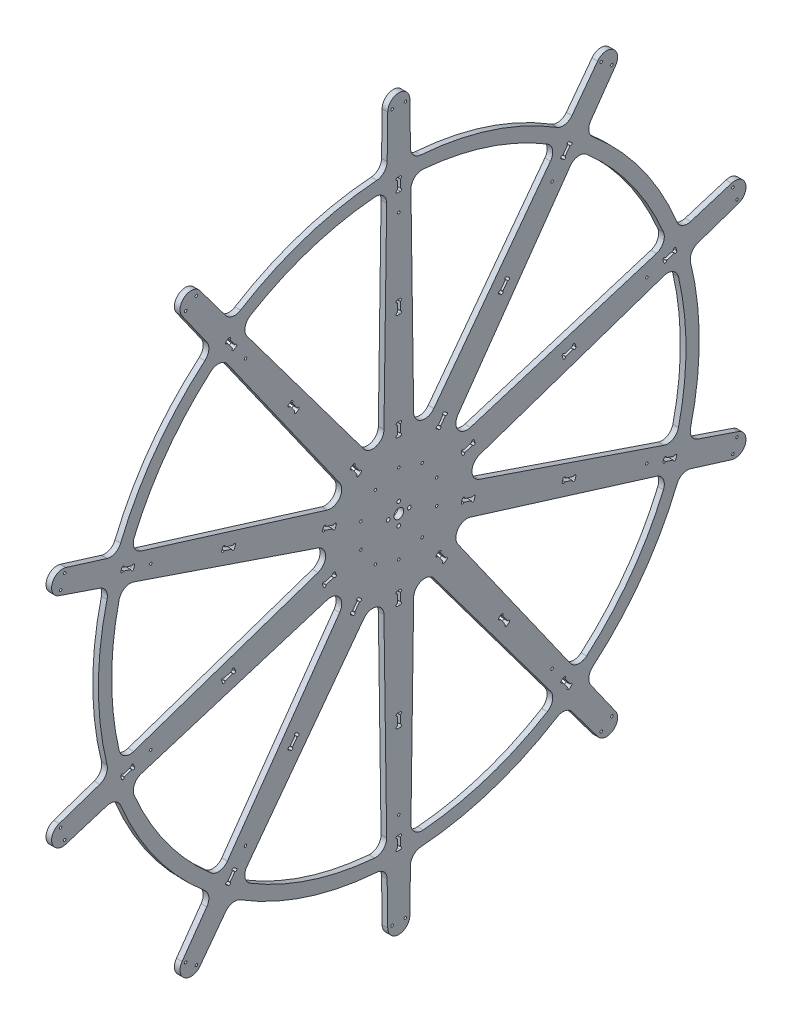
SolidWorks part; units mm, degrees
material "MDF"
ref_plane "Front Plane" through (0, 0, 0) normal (0, 0, 1) x (1, 0, 0)
ref_plane "Top Plane" through (0, 0, 0) normal (0, 1, 0) x (1, 0, 0)
ref_plane "Right Plane" through (0, 0, 0) normal (1, 0, 0) x (0, 0, -1)
sketch "Sketch1" plane through (0, 0, 0) normal (1, 0, 0) x (0, 0, -1)
  line L0 (0, 0) -> (0, -400) construction
  line L1 (-12.5, -400) -> (12.5, -400)
  line L2 (12.5, -400) -> (17.5, -41.4578)
  line L3 (-12.5, -400) -> (-17.5, -41.4578)
  line L4 (0, 0) -> (0, 12) construction
  line L5 (-1.6875, -210.2) -> (1.6875, -210.2)
  line L6 (-1.6875, -90.2) -> (1.6875, -90.2)
  line L7 (-1.6875, -90.2) -> (-1.6875, -75)
  line L8 (-1.6875, -75) -> (1.6875, -75)
  line L9 (1.6875, -90.2) -> (1.6875, -75)
  line L10 (-1.6875, -90.2) -> (1.6875, -75) construction
  line L11 (-1.6875, -75) -> (1.6875, -90.2) construction
  line L12 (-1.6875, -210.2) -> (-1.6875, -195)
  line L13 (-1.6875, -195) -> (1.6875, -195)
  line L14 (1.6875, -210.2) -> (1.6875, -195)
  line L15 (-1.6875, -210.2) -> (1.6875, -195) construction
  line L16 (-1.6875, -195) -> (1.6875, -210.2) construction
  line L17 (-1.6875, -330.2) -> (1.6875, -330.2)
  line L18 (-1.6875, -330.2) -> (-1.6875, -315)
  line L19 (-1.6875, -315) -> (1.6875, -315)
  line L20 (1.6875, -330.2) -> (1.6875, -315)
  line L21 (-1.6875, -330.2) -> (1.6875, -315) construction
  line L22 (-1.6875, -315) -> (1.6875, -330.2) construction
  line L23 (0, -82.6) -> (0, -202.6) construction
  circle A0 centre (0, 0) radius 45
  circle A1 centre (0, 0) radius 12 construction
  circle A2 centre (0, -400) radius 12.5
  circle A15 centre (1.6875, -76.397) radius 1.397
  circle A16 centre (-1.6875, -76.397) radius 1.397
  circle A17 centre (-1.6875, -88.803) radius 1.397
  circle A18 centre (1.6875, -88.803) radius 1.397
  circle A19 centre (1.6875, -196.397) radius 1.397
  circle A20 centre (-1.6875, -196.397) radius 1.397
  circle A21 centre (-1.6875, -208.803) radius 1.397
  circle A22 centre (1.6875, -208.803) radius 1.397
  circle A23 centre (1.6875, -316.397) radius 1.397
  circle A24 centre (-1.6875, -316.397) radius 1.397
  circle A25 centre (-1.6875, -328.803) radius 1.397
  circle A26 centre (1.6875, -328.803) radius 1.397
  point P8 (0, -400)
  point P12 (0, -82.6)
  point P18 (0, -322.6)
  point P19 (0, -202.6)
  point P28 (-7.5, -400)
  point P30 (7.5, -400)
  dimension "D2" = 24
  dimension "D5" = 90
  dimension "D6" = 12.5
  dimension "D13" = 2.794
  dimension "D1" = 400
  dimension "D3" = 25
  dimension "D4" = 35
  dimension "D7" = 15.2
  dimension "D8" = 3.375
  dimension "D9" = 75
  dimension "D11" = 120
  dimension "D12" = 5
  dimension "D10" = 3
extrude "Boss-Extrude1" add sketch "Sketch1" along normal mid plane 6.35 contours A0 region at (0, 0, 0)
extrude "Boss-Extrude2" add sketch "Sketch1<4>" against normal up to surface (3.175 mm away) from surface contours A0 L3 L1 L2 | L5 L14 L13 L12 | L17 L20 L19 L18 | L6 L9 L8 L7 | A2 | A0 region at (0, -220.6787, 11.3979) region at (0, -202.6, 0) region at (0, -82.6, 0) region at (0, -322.6, 0) up to face at (-3.175, 0, -45) starting at face at (3.175, 0, -45)
sketch "Sketch1<4>" plane through (0, 0, 0) normal (1, 0, 0) x (0, 0, -1) same geometry as "Sketch1"
sketch "Sketch2" plane through (0, 0, 0) normal (1, 0, 0) x (0, 0, -1)
  circle A0 centre (0, 0) radius 340
  circle A1 centre (0, 0) radius 325
  point P6 (0, -340)
  dimension "D1" = 60
  dimension "D2" = 15
extrude "Boss-Extrude3" add sketch "Sketch2" against normal up to surface (3.175 mm away) from surface contours A0 A1 region at (0, 0, 330.3833) up to face at (-3.175, -202.2395, 0) starting at face at (3.175, -202.2395, 0)
sketch "Sketch3" plane through (-3.175, 0, 0) normal (1, 0, 0) x (0, 0, -1)
  point P0 (0, 12)
extrude "Cut-Extrude1" cut sketch "Sketch1<5>" against normal through all both and the other way through all contours L18 A25 | L20 A26 | L9 L8 L7 L6 | L14 L13 L12 L5 | L20 L19 L18 L17 region at (0, -328.803, 2.2804) region at (0, -328.803, -2.2804)
sketch "Sketch1<5>" plane through (0, 0, 0) normal (1, 0, 0) x (0, 0, -1) same geometry as "Sketch1"
fillet "Fillet3" radius 12.7 4 edges at (0, -339.7382, -13.3404) (0, -324.7174, -13.5498) (0, -339.7382, 13.3404) (0, -324.7174, 13.5498)
fillet "Fillet4" radius 0.5 12 edges at (0, -327.406, -1.6875) (0, -317.794, -1.6875) (0, -327.406, 1.6875) (0, -317.794, 1.6875) (0, -207.406, 1.6875) (0, -197.794, 1.6875) (0, -207.406, -1.6875) (0, -197.794, -1.6875) (0, -87.406, -1.6875) (0, -87.406, 1.6875) (0, -77.794, 1.6875) (0, -77.794, -1.6875)
sketch "Sketch5" plane through (3.175, 0, 0) normal (1, 0, 0) x (0, 0, -1)
  point P0 (-7.5, -400)
  point P3 (7.5, -400)
hole_wizard "#35 (0.11) Diameter Hole1" positions "Sketch5" profile "Sketch6" hole size "#35" standard "ANSI Inch" end condition through all
sketch "Sketch6" plane through (3.175, -400, 7.5) normal (0, 1, 0) x (0, 0, -1)
  line L0 (0, 0) -> (0, 6.35)
  line L1 (0, 6.35) -> (1.397, 6.35)
  line L2 (1.397, 6.35) -> (1.397, 0)
  line L5 (1.397, 0) -> (0, 0)
  line L11 (0, -6.35) -> (0, 107.95) construction
  dimension "Thru Hole Dia." = 2.794
  dimension "Thru Hole Depth" = 6.35
sketch "Sketch10" plane through (-3.175, 0, 0) normal (-1, 0, 0) x (0, 0, 1)
  line L0 (0, -295.1) -> (0, -45.1) construction
  line L1 (1.5875, -43.8) -> (1.5875, -46.4) construction
  line L2 (1.5875, -293.8) -> (1.5875, -296.4) construction
  point P0 (0, -295.1)
  point P1 (0, -45.1)
  point P6 (1.5875, -45.1)
  point P9 (1.5875, -295.1)
  point P17 (0, -45.1)
  point P19 (0, -295.1)
pattern_circular "CirPattern1" count 10 over 360 about axis through (3.175, 0, 0) along (-1, 0, 0) of "Boss-Extrude2", "Cut-Extrude1", "#35 (0.11) Diameter Hole1", "Fillet3", "Fillet4"
hole_wizard "M4 Clearance Hole1" positions "Sketch3" profile "Sketch4" hole size "M4" standard "ANSI Metric" end condition through all
sketch "Sketch4" plane through (-3.175, 12, 0) normal (0, 1, 0) x (0, 0, 1)
  line L0 (0, 0) -> (0, 6.35)
  line L1 (0, 6.35) -> (2.05, 6.35)
  line L2 (2.05, 6.35) -> (2.05, 0.1888)
  line L3 (2.05, 0.1888) -> (2.275, 0)
  line L5 (2.275, 0) -> (0, 0)
  line L6 (-2.05, 0.1888) -> (-2.275, 0) construction
  line L11 (0, -6.35) -> (0, 107.95) construction
  dimension "Thru Hole Dia." = 4.1
  dimension "Thru Hole Depth" = 6.35
  dimension "Near C'Sink Dia." = 4.55
  dimension "Near C'Sink Angle" = 100
pattern_circular "CirPattern2" count 4 over 360 about axis through (-964.8402, 0, 0) along (1, 0, 0) of "M4 Clearance Hole1"
hole_wizard "#35 (0.11) Diameter Hole2" positions "Sketch10" profile "Sketch11" hole size "#35" standard "ANSI Inch" end condition through all
sketch "Sketch11" plane through (-3.175, -295.1, 0) normal (0, 1, 0) x (0, 0, 1)
  line L0 (0, 0) -> (0, 6.35)
  line L1 (0, 6.35) -> (1.397, 6.35)
  line L2 (1.397, 6.35) -> (1.397, 0.5328)
  line L3 (1.397, 0.5328) -> (2.032, 0)
  line L5 (2.032, 0) -> (0, 0)
  line L6 (-1.397, 0.5328) -> (-2.032, 0) construction
  line L11 (0, -6.35) -> (0, 107.95) construction
  dimension "Thru Hole Dia." = 2.794
  dimension "Thru Hole Depth" = 6.35
  dimension "Near C'Sink Dia." = 4.064
  dimension "Near C'Sink Angle" = 100
sketch "Sketch7" plane through (3.175, 0, 0) normal (1, 0, 0) x (0, 0, -1)
  circle A0 centre (0, 0) radius 5.5
  dimension "D1" = 11
extrude "Cut-Extrude2" cut sketch "Sketch7" against normal through all both and the other way through all
fillet "Fillet1" radius 12.7 10 edges at (0, -53.3491, 17.3342) (0, -53.3491, -17.3342) (0, -32.9716, -45.3815) (0, 0, -56.0946) (0, 32.9716, -45.3815) (0, 53.3491, -17.3342) (0, 53.3491, 17.3342) (0, 32.9716, 45.3815) (0, 0, 56.0946) (0, -32.9716, 45.3815)
pattern_circular "CirPattern3" count 10 over 360 about axis through (-3.175, 0, 0) along (1, 0, 0) of "#35 (0.11) Diameter Hole2"
equation "\"D6@Sketch1\"=\"D3@Sketch1\"/2"
